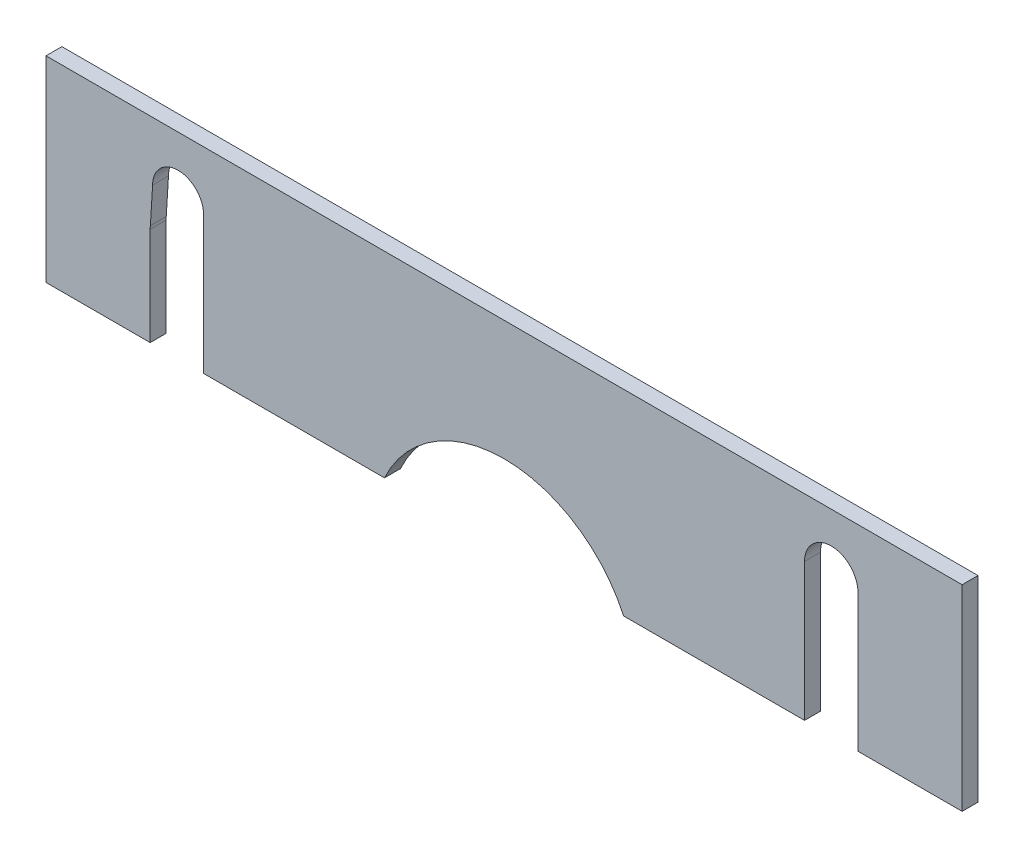
SolidWorks part; units mm, degrees
ref_plane "Front Plane" through (0, 0, 0) normal (0, 0, 1) x (1, 0, 0)
ref_plane "Top Plane" through (0, 0, 0) normal (0, 1, 0) x (1, 0, 0)
ref_plane "Right Plane" through (0, 0, 0) normal (1, 0, 0) x (0, 0, -1)
sketch "Sketch1" plane through (0, 0, 0) normal (0, 0, 1) x (1, 0, 0)
  line L0 (0, 26.0231) -> (0, -17.8145) construction
  line L1 (-35, 7.5) -> (35, 7.5)
  line L2 (-35, 7.5) -> (-35, -7.5)
  line L3 (-35, -7.5) -> (35, -7.5)
  line L4 (35, 7.5) -> (35, -7.5)
  line L5 (-35, 7.5) -> (35, -7.5) construction
  line L6 (-35, -7.5) -> (35, 7.5) construction
  circle A0 centre (-25, 0) radius 2.04
  circle A1 centre (25, 0) radius 2.04
  point P0 (0, 0)
  dimension "D3" = 50
  dimension "D4" = 4.08
  dimension "D1" = 15
  dimension "D2" = 70
base flange "Base-Flange1" sketch "Sketch1" thickness 1.2141 reverse thickness direction no parameters "D1"=1.27
sketch "Sketch3" plane through (0, 0, 0) normal (0, 0, 1) x (1, 0, 0)
  circle A0 centre (0, -11.7284) radius 10.0679
extrude "Cut-Extrude1" cut sketch "Sketch3" against normal blind 10 normal cut yes
sketch "Sketch4" plane through (0, 0, -1.2141) normal (0, 0, -1) x (-1, 0, 0)
  line L0 (27.04, 0) -> (27.04, -7.5)
  line L1 (35, -7.5) -> (9.1369, -7.5) construction
  line L2 (27.04, -7.5) -> (22.96, -7.5)
  line L3 (22.96, -7.5) -> (22.96, 0)
  line L4 (22.96, 0) -> (22.96, 3.0222)
  line L6 (26.8548, 3.0222) -> (27.04, 0)
  line L8 (-22.96, 0) -> (-22.96, -7.5)
  line L9 (-9.1369, -7.5) -> (-35, -7.5) construction
  line L10 (-22.96, -7.5) -> (-27.04, -7.5)
  line L11 (-27.04, -7.5) -> (-27.04, 0)
  line L12 (-27.04, 0) -> (-27.04, 3.0222)
  line L14 (-22.96, 3.0222) -> (-22.96, 0)
  circle A0 centre (25, 0) radius 2.04 construction
  circle A1 centre (-25, 0) radius 2.04 construction
  arc A2 (26.8548, 3.0222) -> (22.96, 3.0222) centre (24.9074, 3.0222) ccw
  arc A3 (-22.96, 3.0222) -> (-27.04, 3.0222) centre (-25, 3.0222) ccw
extrude "Cut-Extrude2" cut sketch "Sketch4" against normal blind 10 normal cut yes
sketch "Bend-Lines1" [suppressed] plane through (0, 0, 0) normal (0, 1, 0) x (1, 0, 0)
sketch "Bounding-Box1" [suppressed] plane through (0, 0, 0) normal (0, 1, 0) x (1, 0, 0)
sheet metal parameters "Sheet-Metal1" thickness 1.2141 parameters "D1"=1.27
flat pattern "Flat-Pattern1" [suppressed]
sketch "Bend-Lines2" plane through (0, 0, 0) normal (0, 1, 0) x (1, 0, 0)
sketch "Bounding-Box2" [suppressed] plane through (0, 0, 0) normal (0, 1, 0) x (1, 0, 0)
sheet metal parameters "Sheet-Metal2" thickness 1.2141 parameters "D1"=1.27
flat pattern "Flat-Pattern1"
sketch "Bend-Lines2" plane through (0, 0, 0) normal (0, 1, 0) x (1, 0, 0)
sketch3d "Bounding-Box2" [suppressed]
  line L0 (-35, -7.5, 0) -> (35, -7.5, 0) construction
  line L1 (-35, 7.5, 0) -> (35, 7.5, 0) construction
  line L2 (-35, -7.5, 0) -> (-35, 7.5, 0) construction
  line L3 (35, -7.5, 0) -> (35, 7.5, 0) construction
sheet metal parameters "Sheet-Metal3" thickness 1.2141 parameters "D1"=1.27
flat pattern "Flat-Pattern1"
sketch "Bend-Lines2" plane through (0, 0, 0) normal (0, 1, 0) x (1, 0, 0)
sketch3d "Bounding-Box2" [suppressed]
  line L0 (-35, -7.5, 0) -> (35, -7.5, 0) construction
  line L1 (-35, 7.5, 0) -> (35, 7.5, 0) construction
  line L2 (-35, -7.5, 0) -> (-35, 7.5, 0) construction
  line L3 (35, -7.5, 0) -> (35, 7.5, 0) construction
